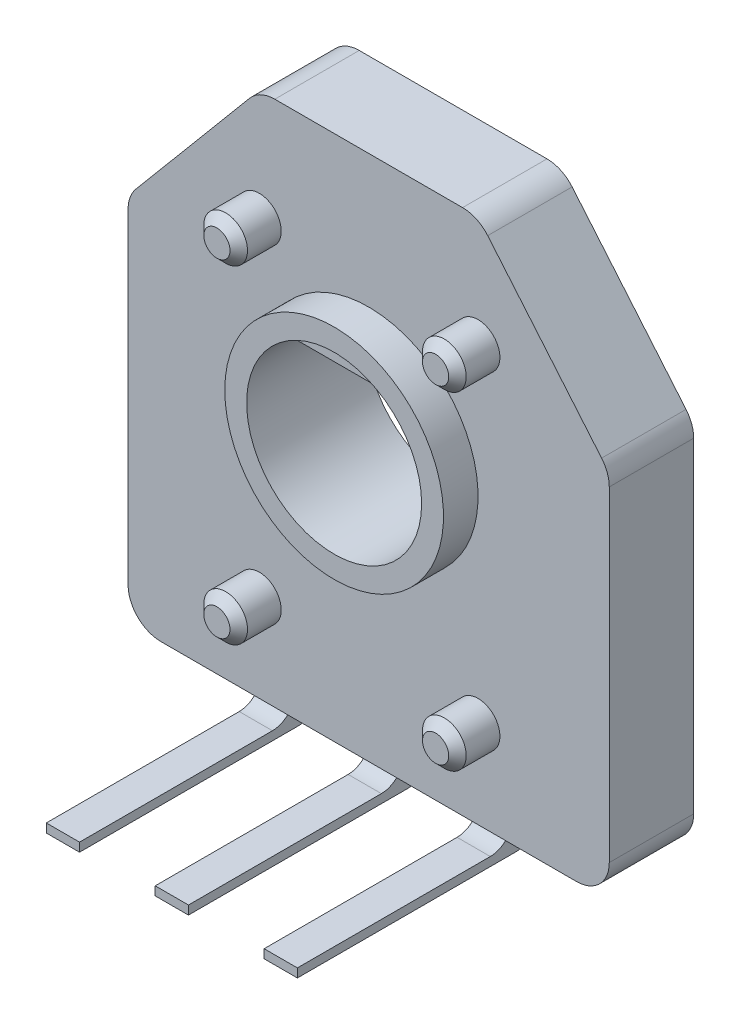
SolidWorks part; units mm, degrees
ref_plane "Front Plane" through (0, 0, 0) normal (0, 0, 1) x (1, 0, 0)
ref_plane "Top Plane" through (0, 0, 0) normal (0, 1, 0) x (1, 0, 0)
ref_plane "Right Plane" through (0, 0, 0) normal (1, 0, 0) x (0, 0, -1)
sketch "Sketch1" plane through (0, 0, 0) normal (0, 0, 1) x (1, 0, 0)
  line L0 (5.5, 0) -> (5.5, -6.5)
  line L1 (5.5, -6.5) -> (-5.5, -6.5)
  line L2 (-5.5, -6.5) -> (-5.5, 0)
  line L3 (-5.5, 0) -> (5.5, 0) construction
  line L4 (-5.5, 0) -> (-5.5, 1.96)
  line L5 (-5.5, 1.96) -> (-2.496, 5.54)
  line L6 (-2.496, 5.54) -> (2.496, 5.54)
  line L7 (2.496, 5.54) -> (5.5, 1.96)
  line L8 (5.5, 1.96) -> (5.5, 0)
  line L9 (-5.5, 1.96) -> (-5.5, 12.411) construction
  line L10 (-1.7186, 1.023) -> (1.7186, 1.023)
  arc A0 (-1.7186, 1.023) -> (1.7186, 1.023) centre (0, 0) ccw
  point P6 (0, -6.5)
  point P12 (0, 0)
  point P16 (0, -2)
  dimension "D1" = 4
  dimension "D2" = 11
  dimension "D3" = 6.5
  dimension "D4" = 5.54
  dimension "D5" = 3.58
  dimension "D6" = 40
  dimension "D7" = 3.023
extrude "Boss-Extrude1" add sketch "Sketch1" along normal blind 1.93
sketch "Sketch2" plane through (0, 0, 1.93) normal (0, 0, 1) x (1, 0, 0)
  circle A0 centre (0, 0) radius 2 construction
  circle A1 centre (0, 0) radius 2
  circle A2 centre (0, 0) radius 2.5
  dimension "D1" = 0.5
extrude "Boss-Extrude2" add sketch "Sketch2" along normal blind 0.79
sketch "Sketch3" plane through (0, 0, 1.93) normal (0, 0, 1) x (1, 0, 0)
  line L0 (0, -6.5) -> (2.49, -6.5) construction
  line L1 (-2.49, -6.5) -> (0, -6.5) construction
  line L5 (-5.5, -6.5) -> (5.5, -6.5) construction
  line L6 (-0.38, -6.5) -> (0.38, -6.5)
  line L7 (-0.38, -6.5) -> (-0.38, -7.1)
  line L8 (-0.38, -7.1) -> (0.38, -7.1)
  line L9 (0.38, -6.5) -> (0.38, -7.1)
  line L10 (2.11, -6.5) -> (2.11, -7.1)
  line L11 (2.11, -6.5) -> (2.87, -6.5)
  line L12 (2.87, -6.5) -> (2.87, -7.1)
  line L13 (2.11, -7.1) -> (2.87, -7.1)
  line L14 (-2.87, -6.5) -> (-2.87, -7.1)
  line L15 (-2.87, -6.5) -> (-2.11, -6.5)
  line L16 (-2.11, -6.5) -> (-2.11, -7.1)
  line L17 (-2.87, -7.1) -> (-2.11, -7.1)
  point P12 (0, -6.5)
  dimension "D1" = 0.6
  dimension "D2" = 0.76
  dimension "D5" = 2.49
  dimension "D6" = 2.49
  dimension "D3" = 2
  dimension "D4" = 2
extrude "Boss-Extrude3" add sketch "Sketch3" along normal blind 4.5 and the other way blind 1
fillet "Fillet2" radius 0.75 6 edges at (5.5, -6.5, 0.965) (5.5, 1.96, 0.965) (2.496, 5.54, 0.965) (-2.496, 5.54, 0.965) (-5.5, -6.5, 0.965) (-5.5, 1.96, 0.965)
sketch "Sketch4" plane through (0, 0, 6.43) normal (0, 0, 1) x (1, 0, 0)
  line L0 (2.87, -7.1) -> (2.87, -6.5) construction
  line L1 (-2.87, -6.5) -> (2.87, -6.5)
  line L2 (-2.87, -6.5) -> (-2.87, -6.9)
  line L3 (-2.87, -6.9) -> (2.87, -6.9)
  line L4 (2.87, -6.5) -> (2.87, -6.9)
  dimension "D1" = 0.4
extrude "Cut-Extrude1" cut sketch "Sketch4" against normal offset from surface (4.9 mm away) 0.4 up to face at (0, -1.9064, 1.93) offset beyond the face yes
fillet "Fillet1" radius 0.5 6 edges at (2.49, -7.1, 0.93) (0, -7.1, 0.93) (-2.49, -7.1, 0.93) (2.49, -6.9, 1.53) (0, -6.9, 1.53) (-2.49, -6.9, 1.53)
sketch "Sketch5" plane through (0, 0, 1.93) normal (0, 0, 1) x (1, 0, 0)
  line L1 (-2.5, -4.5) -> (2.5, -4.5) construction
  line L2 (-2.5, -4.5) -> (-2.5, 3) construction
  line L3 (-2.5, 3) -> (2.5, 3) construction
  line L4 (2.5, -4.5) -> (2.5, 3) construction
  line L5 (-2.5, -4.5) -> (2.5, 3) construction
  line L6 (-2.5, 3) -> (2.5, -4.5) construction
  circle A0 centre (-2.5, -4.5) radius 0.5
  circle A1 centre (2.5, -4.5) radius 0.5
  circle A2 centre (2.5, 3) radius 0.5
  circle A3 centre (-2.5, 3) radius 0.5
  point P0 (0, -0.75)
  dimension "D4" = 1
  dimension "D1" = 5
  dimension "D2" = 7.5
  dimension "D3" = 3
extrude "Boss-Extrude4" add sketch "Sketch5" along normal blind 0.97
chamfer "Chamfer1" distance 0.2 angle 45 4 edges at (-2, -4.5, 2.9) (3, -4.5, 2.9) (3, 3, 2.9) (-2, 3, 2.9)
